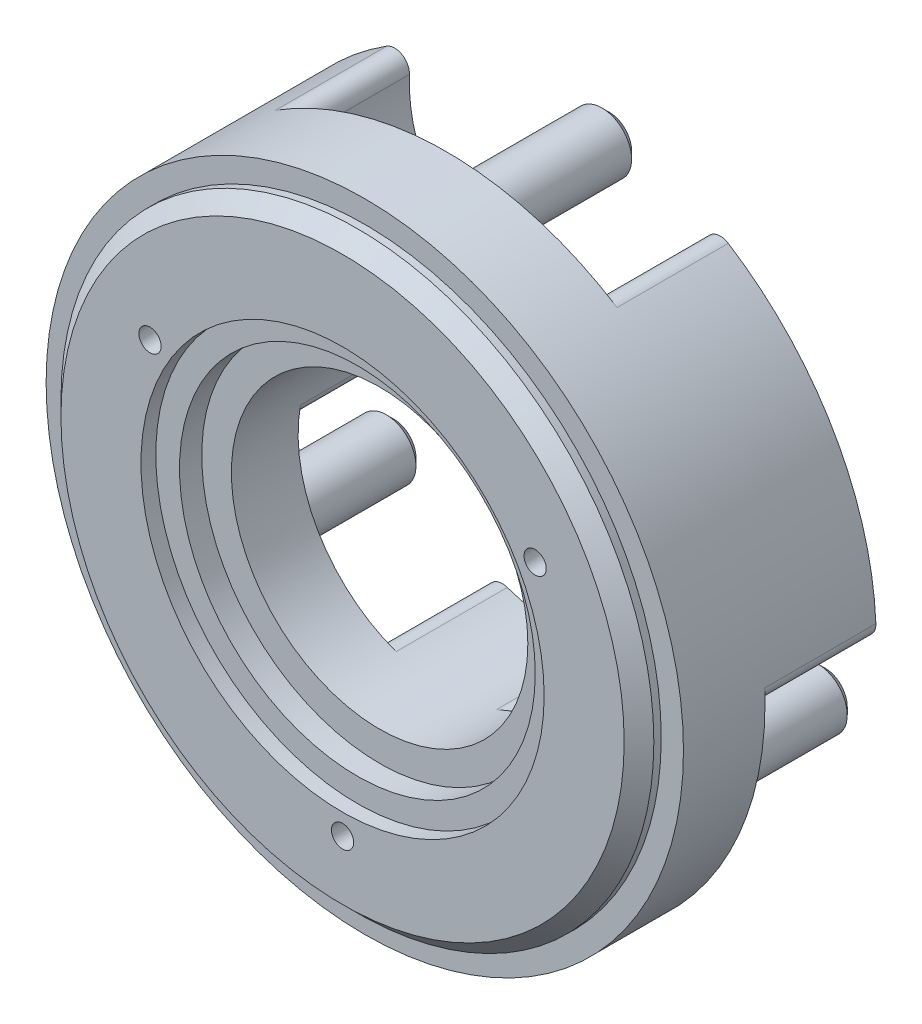
SolidWorks part; units mm, degrees
note: The reader was unsure of these and kept them because the rebuilt part matched: shared geometry of "Sketch7<3>".
ref_plane "Front Plane" through (0, 0, 0) normal (0, 0, 1) x (1, 0, 0)
ref_plane "Top Plane" through (0, 0, 0) normal (0, 1, 0) x (1, 0, 0)
ref_plane "Right Plane" through (0, 0, 0) normal (1, 0, 0) x (0, 0, -1)
sketch "Sketch3" plane through (0, 0, 0) normal (1, 0, 0) x (0, 0, -1)
  line L0 (0, 0) -> (0, 21.6269) construction
  line L1 (0, 0) -> (18.9047, 0) construction
  line L12 (1, 13.6) -> (1, 12)
  line L13 (0, 13.6) -> (1, 13.6)
  line L14 (1, 12) -> (2.5, 12)
  line L15 (2.5, 12) -> (2.5, 10)
  line L16 (2.5, 10) -> (7, 10)
  line L17 (7, 10) -> (7, 21.5)
  line L18 (7, 21.5) -> (1.5, 21.5)
  line L19 (1.5, 21.5) -> (1.5, 20)
  line L20 (1.5, 20) -> (0, 20)
  line L21 (0, 20) -> (0, 13.6)
  dimension "D1" = 13.6
  dimension "D2" = 12
  dimension "D3" = 10
  dimension "D4" = 21.5
  dimension "D5" = 20
  dimension "D6" = 3
  dimension "D7" = 5.5
  dimension "D8" = 1
  dimension "D9" = 2.5
revolve "Revolve1" add sketch "Sketch3" angle 360 about L1
sketch "Sketch4" plane through (0, 0, -7) normal (0, 0, -1) x (-1, 0, 0)
  circle A0 centre (0, 0) radius 15 construction
  circle A1 centre (0, 0) radius 21.5
  circle A2 centre (0, 0) radius 21.5
  circle A3 centre (0, 0) radius 16.8 construction
  circle A5 centre (0, 16.8) radius 4
  point P8 (0, 16.8)
  point P9 (0, 0)
  point P10 (0, 16.8)
  dimension "D2" = 30
  dimension "D3" = 33.6
  dimension "D4" = 8
  dimension "D1" = 0
extrude "Boss-Extrude1" add sketch "Sketch4" along normal blind 0.5 contours A5
sketch "Sketch5" plane through (0, 0, -7.5) normal (0, 0, -1) x (-1, 0, 0)
  circle A0 centre (0, 16.8) radius 2
  circle A1 centre (0, 16.8) radius 4
  circle A2 centre (0, 16.8) radius 4
  dimension "D2" = 4
  dimension "D1" = 0
extrude "Boss-Extrude2" add sketch "Sketch5" along normal blind 10.5 contours A0
chamfer "Chamfer1" distance 0.5 angle 45 1 edges at (-2, 16.8, -18)
pattern_circular "CirPattern1" count 3 over 360 about axis through (0, 0, 0) along (0, 0, 1) of "Chamfer1", "Boss-Extrude2", "Boss-Extrude1"
sketch "Sketch6" plane through (0, 0, -7) normal (0, 0, -1) x (-1, 0, 0)
  line L0 (0, 0) -> (0, -26.5877) construction
  line L1 (0, 0) -> (42.2681, 0) construction
  circle A1 centre (0, 0) radius 21.5
  circle A2 centre (0, 0) radius 21.5
  circle A3 centre (-14.5492, -8.4) radius 1.5
  circle A4 centre (-14.5492, -8.4) radius 1.5
  circle A5 centre (14.5492, -8.4) radius 1.5
  circle A6 centre (14.5492, -8.4) radius 1.5
  circle A9 centre (0, 0) radius 10 construction
  circle A10 centre (0, 0) radius 10
  arc A11 (-11.7553, -18.0018) -> (-4.5617, -8.8989) centre (-14.5492, -8.4) ccw
  arc A12 (4.5617, -8.8989) -> (11.7553, -18.0018) centre (14.5492, -8.4) ccw
  circle M11 centre (0, 0) radius 21.5
  dimension "D4" = 10
  dimension "D1" = 0
  dimension "D2" = 0
  dimension "D3" = 0
extrude "Boss-Extrude3" add sketch "Sketch6" along normal blind 7.5 contours A12 A10 A11 M11
sketch "Sketch7" plane through (0, 0, -14.5) normal (0, 0, -1) x (-1, 0, 0)
  line L2 (0, 0) -> (-4.6587, -17.3867)
  line L3 (4.6587, -17.3867) -> (0, 0)
  line L4 (0, 0) -> (0, -27.9066) construction
  arc A0 (-3.1058, -11.5911) -> (3.1058, -11.5911) centre (0, 0) ccw
  arc A1 (-4.6587, -17.3867) -> (4.6587, -17.3867) centre (0, 0) ccw
  circle A2 centre (0, -15) radius 0.75
  dimension "D1" = 18
  dimension "D2" = 12
  dimension "D5" = 1.5
  dimension "D3" = 30
  dimension "D4" = 15
  dimension "D6" = 15
extrude "Cut-Extrude1" cut sketch "Sketch7" against normal blind 2 contours A0 L4 A1 L3 | L4 A0 L2 A1
extrude "Cut-Extrude2" cut sketch "Sketch7<3>" against normal through all contours A2 L4 | L4 A2
sketch "Sketch7<3>" plane through (0, 0, -14.5) normal (0, 0, -1) x (-1, 0, 0) same geometry as "Sketch7"
chamfer "Chamfer2" distance 0.2 angle 45 1 edges at (-0.75, -15, -12.5)
chamfer "Chamfer3" distance 0.5 angle 45 4 edges at (0, -18, -14.5) (3.8823, -14.4889, -14.5) (0, -12, -14.5) (-3.8823, -14.4889, -14.5)
pattern_circular "CirPattern2" count 3 over 360 about axis through (0, 0, 0) along (0, 0, 1) of "Chamfer3", "Chamfer2", "Cut-Extrude2", "Cut-Extrude1", "Boss-Extrude3"
chamfer "Chamfer4" distance 1 angle 45 1 edges at (20, 0, 0)
fillet "Fillet1" radius 1 12 edges at (21.4676, -1.1795, -10.75) (9.9875, 0.4989, -10.75) (5.4259, 8.4, -10.75) (9.7123, 19.1813, -10.75) (-9.7123, 19.1812, -10.75) (-5.4259, 8.4, -10.75) (-9.9875, 0.4989, -10.75) (-21.4676, -1.1795, -10.75) (-11.7553, -18.0018, -10.75) (-4.5617, -8.8989, -10.75) (4.5617, -8.8989, -10.75) (11.7553, -18.0018, -10.75)
